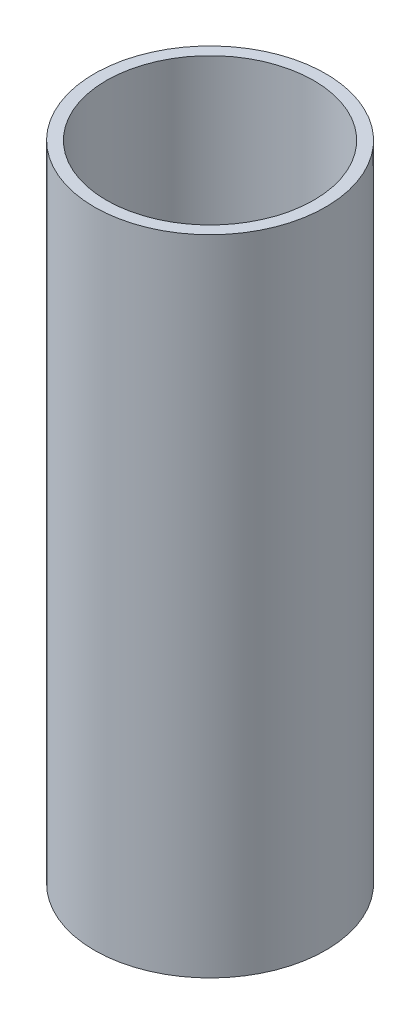
SolidWorks part; units mm, degrees
ref_plane "Front Plane" through (0, 0, 0) normal (0, 0, 1) x (1, 0, 0)
ref_plane "Top Plane" through (0, 0, 0) normal (0, 1, 0) x (1, 0, 0)
ref_plane "Right Plane" through (0, 0, 0) normal (1, 0, 0) x (0, 0, -1)
sketch "Sketch1" plane through (0, 0, 0) normal (0, 1, 0) x (1, 0, 0)
  circle A0 centre (0, 0) radius 55
  dimension "SLEEVE_OD" = 110
extrude "Boss-Extrude1" add sketch "Sketch1" along normal blind 306.2002
sketch "Sketch2" plane through (0, 0, 0) normal (0, 1, 0) x (1, 0, 0)
  circle A0 centre (0, 0) radius 49.3353
  dimension "BORE_D" = 98.6706
extrude "Cut-Extrude1" cut sketch "Sketch2" along normal through all
chamfer "Chamfer1" distance 2.3647 angle 60 rebuild error yes
